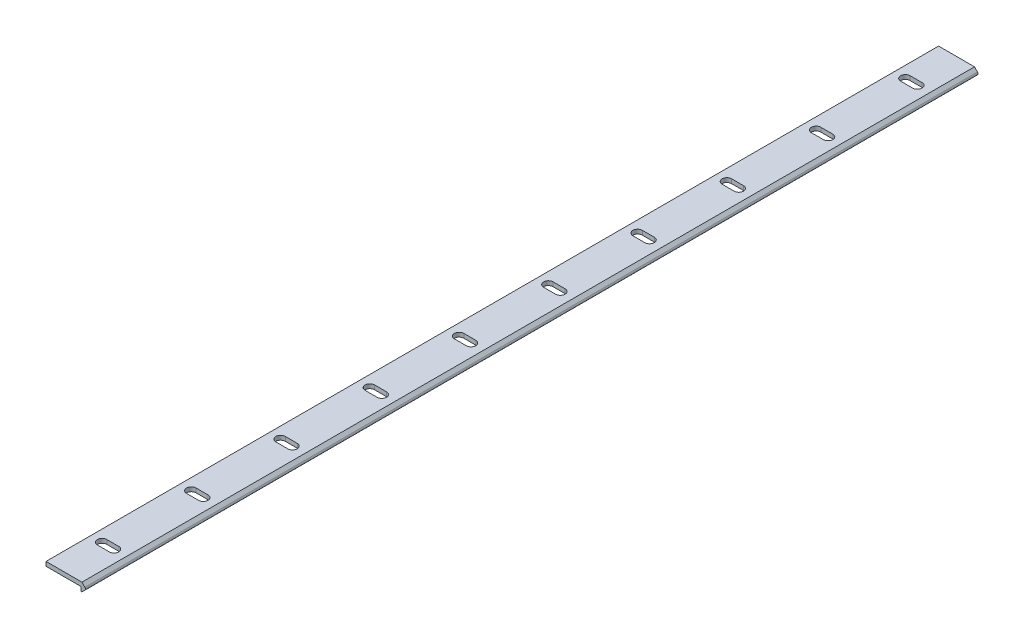
SolidWorks part; units mm, degrees
material "6061-T6 (SS)"
ref_plane "Front Plane" through (0, 0, 0) normal (0, 0, 1) x (1, 0, 0)
ref_plane "Top Plane" through (0, 0, 0) normal (0, 1, 0) x (1, 0, 0)
ref_plane "Right Plane" through (0, 0, 0) normal (1, 0, 0) x (0, 0, -1)
sketch "Sketch1" plane through (0, 0, 0) normal (0, 0, 1) x (1, 0, 0)
  line L0 (19.5291, 0) -> (19.5291, 4.75) construction
  line L1 (0, 0) -> (22.497, 0) construction
  line L2 (0, 0) -> (0, 4.75) construction
  line L3 (0, 4.75) -> (22.497, 4.75) construction
  line L4 (22.497, 0) -> (22.497, 4.75) construction
  line L5 (19.5291, 2.375) -> (0, 2.375)
  line L6 (19.5291, 2.375) -> (19.5291, 0)
  line L7 (19.5291, 4.75) -> (20.122, 4.75)
  line L8 (20.122, 4.75) -> (22.497, 2.375)
  line L9 (19.5291, 4.75) -> (0, 4.75)
  line L10 (0, 4.75) -> (0, 2.375)
  line L11 (22.497, 2.375) -> (20.122, 0)
  line L12 (20.122, 0) -> (19.5291, 0)
  dimension "D1" = 22.497
  dimension "D2" = 4.75
  dimension "D3" = 19.5291
  dimension "D4" = 90
extrude "Boss-Extrude1" add sketch "Sketch1" along normal blind 500
sketch "Sketch2" plane through (0, 4.75, 0) normal (0, 1, 0) x (1, 0, 0)
  line L0 (0, -500) -> (0, 0) construction
  line L1 (20.122, 0) -> (0, 0) construction
  line L2 (6.4087, -25) -> (9.7587, -25)
  line L3 (9.7587, -25) -> (13.1087, -25)
  line L4 (6.4087, -22.35) -> (13.1087, -22.35)
  line L5 (13.1087, -27.65) -> (6.4087, -27.65)
  circle A0 centre (9.7587, -25) radius 2.65 construction
  circle A1 centre (13.1087, -25) radius 2.65 construction
  circle A2 centre (6.4087, -25) radius 2.65 construction
  arc A3 (6.4087, -22.35) -> (6.4087, -27.65) centre (6.4087, -25) ccw
  arc A4 (13.1087, -22.35) -> (13.1087, -27.65) centre (13.1087, -25) cw
  point P4 (10.061, 0)
  dimension "D3" = 5.3
  dimension "D1" = 9.7587
  dimension "D2" = 25
  dimension "D4" = 6.7
extrude "Cut-Extrude1" cut sketch "Sketch2" against normal blind 2.375 contours A4 L4 A3 L5 region at (9.7587, 4.75, 22.4812)
pattern_linear "LPattern1" count 10 spacing 50 along (0, 0, 1) of "Cut-Extrude1"
fillet "Fillet1" radius 1 1 edges at (22.497, 2.375, 250)
